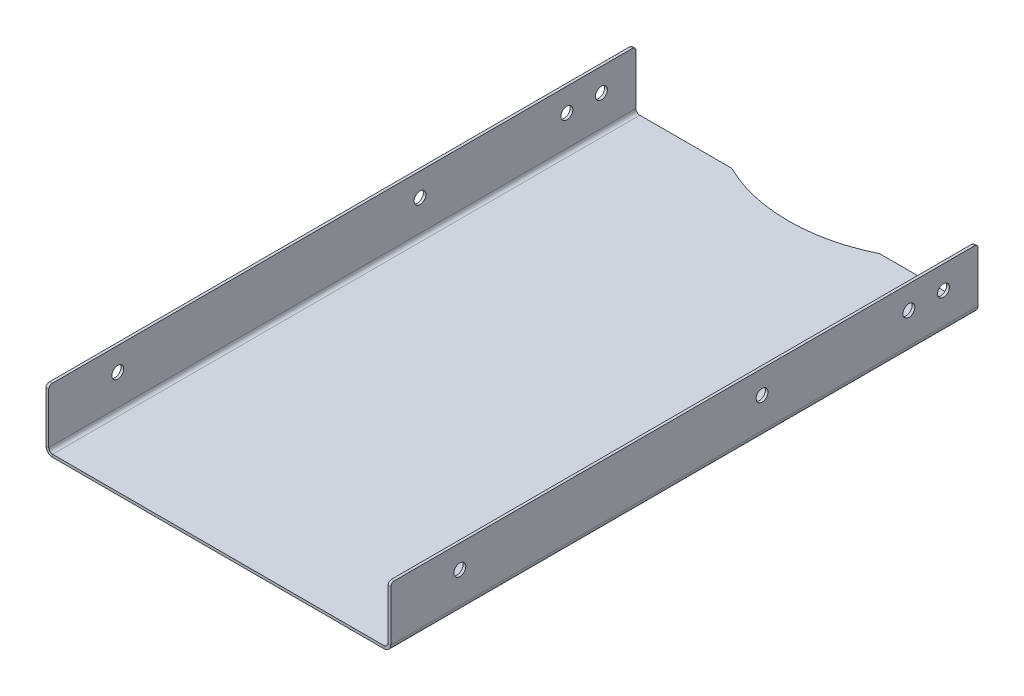
SolidWorks part; units mm, degrees
note: The reader was unsure of these and kept them because the rebuilt part matched: thickness of "Base-Flange1", "Edge-Flange1", "Sheet-Metal1", "Sheet-Metal2", "Sheet-Metal3", "Sheet-Metal4", "Sheet-Metal5", "Sheet-Metal6", "Sheet-Metal7"; flange length of "Edge-Flange1".
material "Plain Carbon Steel"
ref_plane "Front Plane" through (0, 0, 0) normal (0, 0, 1) x (1, 0, 0)
ref_plane "Top Plane" through (0, 0, 0) normal (0, 1, 0) x (1, 0, 0)
ref_plane "Right Plane" through (0, 0, 0) normal (1, 0, 0) x (0, 0, -1)
sketch "Sketch1" plane through (0, 0, 0) normal (0, 1, 0) x (1, 0, 0)
  line L1 (0, 0) -> (253.492, 0)
  line L2 (0, 0) -> (0, 457.2)
  line L3 (0, 457.2) -> (253.492, 457.2)
  line L4 (253.492, 0) -> (253.492, 457.2)
  dimension "D1" = 253.492
  dimension "D2" = 457.2
base flange "Base-Flange1" sketch "Sketch1" thickness 1.9939 reverse thickness direction no parameters "D1"=2.8461
edge flange "Edge-Flange1" sketch "Sketch10" flange profiles "Sketch10", "Sketch11" flange angle 90 flange length 44.45 flange position material inside bend radius 2.8461 thickness 1.9939 relief rectangular parameters "D1"=3, "D6"=10, "D8"=1
sketch "Sketch10" plane through (0, 0, 0) normal (-1, 0, 0) x (0, 0, 1)
  line L2 (-457.2, 0) -> (-457.2, 42.4561)
  line L3 (-457.2, 42.4561) -> (0, 42.4561)
  line L4 (0, 42.4561) -> (0, 0)
  line L7 (-457.2, 0) -> (0, 0) construction
  line L8 (-457.2, 0) -> (0, 0)
sketch "Sketch11" plane through (253.492, 0, 0) normal (1, 0, 0) x (0, 0, -1)
  line L2 (457.2, 0) -> (457.2, 42.4561)
  line L3 (457.2, 42.4561) -> (0, 42.4561)
  line L4 (0, 42.4561) -> (0, 0)
  line L5 (0, 0) -> (457.2, 0) construction
  line L6 (0, 0) -> (457.2, 0)
bend "EdgeBend1" bend radius 2.8461 bend angle 90 parameters "D5"=1
bend "EdgeBend2" bend radius 2.8461 bend angle 90 parameters "D5"=2
hole_wizard "Hole for 1/4 Self-clinching Nuts (S,SS,CLS,CLSS)1" positions "Sketch12" profile "Sketch13" hole size "1/4-20" standard "PEM® Inch" end condition through all
sketch "Sketch12" plane through (0, 0, 0) normal (-1, 0, 0) x (0, 0, 1)
  line L0 (-228.6, 42.4561) -> (-228.6, -1.9939) construction
  line L1 (0, 42.4561) -> (-457.2, 42.4561) construction
  line L2 (0, -1.9939) -> (-457.2, -1.9939) construction
  line L3 (-457.2, 42.4561) -> (-457.2, 2.8461) construction
  line L5 (0, 0) -> (-457.2, 0) construction
  line L6 (0, 0) -> (-457.2, 0) construction
  point P0 (-406.4, 25.4)
  point P26 (-50.8, 25.4)
  point P31 (-381, 25.4)
  point P36 (-273.05, 25.4)
  dimension "D1" = 25.4
  dimension "D2" = 50.8
  dimension "D4" = 107.95
  dimension "D5" = 25.4
sketch "Sketch13" plane through (0, 25.4, -406.4) normal (0, 1, 0) x (0, 0, 1)
  line L0 (0, 0) -> (0, 253.492)
  line L1 (0, 253.492) -> (4.3688, 253.492)
  line L2 (4.3688, 253.492) -> (4.3688, 0)
  line L5 (4.3688, 0) -> (0, 0)
  line L11 (0, -6.35) -> (0, 107.95) construction
  dimension "Thru Hole Dia." = 8.7376
  dimension "Thru Hole Depth" = 253.492
sketch "Sketch14" plane through (0, 0, 0) normal (0, 1, 0) x (1, 0, 0)
  line L0 (4.84, 0) -> (248.652, 0) construction
  line L6 (248.652, 457.2) -> (4.84, 457.2) construction
  line L7 (229.602, 457.2) -> (23.89, 457.2)
  line L8 (229.602, 457.2) -> (229.602, 487.68)
  line L9 (229.602, 487.68) -> (23.89, 487.68)
  line L10 (23.89, 457.2) -> (23.89, 487.68)
  line L11 (4.84, 0) -> (4.84, 457.2) construction
  point P6 (126.746, 0)
  point P9 (126.746, 457.2)
  dimension "D1" = 30.48
  dimension "D2" = 19.05
extrude "Boss-Extrude1" [suppressed] add sketch "Sketch14" against normal up to surface (2.3622 mm away)
sketch "Sketch15" plane through (0, -1.9939, 0) normal (0, -1, 0) x (1, 0, 0)
  line L0 (248.652, -457.2) -> (4.84, -457.2) construction
  line L1 (215.646, -457.2) -> (37.846, -457.2)
  arc A0 (37.846, -457.2) -> (215.646, -457.2) centre (126.746, -541.8667) cw
  point P3 (126.746, -457.2)
  point P9 (126.746, -419.1)
  dimension "D1" = 177.8
  dimension "D2" = 38.1
extrude "Cut-Extrude1" cut sketch "Sketch15" against normal through all normal cut yes
sketch "Sketch16" plane through (0, -1.9939, 0) normal (0, -1, 0) x (1, 0, 0)
  line L0 (253.492, 0) -> (253.492, -457.2) construction
  line L1 (0, -457.2) -> (253.492, -457.2)
  line L2 (0, -457.2) -> (0, -431.8)
  line L3 (0, -431.8) -> (253.492, -431.8)
  line L4 (253.492, -457.2) -> (253.492, -431.8)
  dimension "D1" = 25.4
extrude "Cut-Extrude2" cut sketch "Sketch16" against normal through all normal cut yes
sketch "Sketch17" [suppressed] plane through (0, 0, 0) normal (0, 1, 0) x (1, 0, 0)
  line L0 (121.9835, 0) -> (126.746, 8.2489)
  line L1 (4.7434, 0) -> (248.7485, 0) construction
  line L2 (126.746, 8.2489) -> (131.5085, 0)
  line L3 (131.5085, 0) -> (121.9835, 0)
  line L4 (253.492, 209.5962) -> (0, 209.5962) construction
  line L5 (253.492, 431.8) -> (253.492, 0) construction
  line L6 (0, 0) -> (0, 431.8) construction
  line L7 (131.5085, 419.1924) -> (121.9835, 419.1924)
  line L8 (126.746, 410.9435) -> (131.5085, 419.1924)
  line L9 (121.9835, 419.1924) -> (126.746, 410.9435)
  arc A0 (72.3678, 431.8) -> (181.1242, 431.8) centre (126.746, 541.8667) ccw construction
  point P4 (126.746, 0)
  point P6 (126.746, 419.1924)
  dimension "D1" = 9.525
extrude "Cut-Extrude3" [suppressed] cut sketch "Sketch17" against normal through all
fillet "Fillet1" radius 2.54 4 edges at (0.9969, 42.4561, -431.8) (252.4951, 42.4561, -431.8) (252.4951, 42.4561, 0) (0.9969, 42.4561, 0)
sketch "Bend-Lines1" [suppressed] plane through (0, 0, 0) normal (0, 1, 0) x (1, 0, 0)
sketch "Bounding-Box1" [suppressed] plane through (0, 0, 0) normal (0, 1, 0) x (1, 0, 0)
sheet metal parameters "Sheet-Metal1" thickness 1.9939 parameters "D1"=3, "D7"=2.3622
flat pattern "Flat-Pattern1" [suppressed]
sketch "Bend-Lines2" plane through (0, 0, 0) normal (0, 1, 0) x (1, 0, 0)
sketch3d "Bounding-Box2" [suppressed]
  line L0 (0, 0, 0) -> (0, 609.6, 0) construction
  line L1 (-247.65, 0, 0) -> (-247.65, 609.6, 0) construction
  line L2 (0, 0, 0) -> (-247.65, 0, 0) construction
  line L3 (0, 609.6, 0) -> (-247.65, 609.6, 0) construction
sheet metal parameters "Sheet-Metal2" thickness 1.9939 parameters "D1"=3, "D7"=2.3622
flat pattern "Flat-Pattern1"
sketch "Bend-Lines2" plane through (0, 0, 0) normal (0, 1, 0) x (1, 0, 0)
  line L0 (247.9338, 0) -> (247.9338, 609.6) construction
  line L1 (-0.2838, 609.6) -> (-0.2838, 0) construction
  line L2 (247.9338, 0) -> (247.9338, 609.6) construction
  line L3 (-0.2838, 609.6) -> (-0.2838, 0) construction
sketch3d "Bounding-Box2" [suppressed]
  line L0 (-42.6555, 0, 0) -> (-42.6555, 609.6, 0) construction
  line L1 (290.3055, 0, 0) -> (290.3055, 609.6, 0) construction
  line L2 (-42.6555, 0, 0) -> (290.3055, 0, 0) construction
  line L3 (-42.6555, 609.6, 0) -> (290.3055, 609.6, 0) construction
bend of the flat pattern "Flatten-<EdgeBend1>1"
bend of the flat pattern "Flatten-<EdgeBend2>1"
sheet metal parameters "Sheet-Metal3" thickness 1.9939 parameters "D1"=3, "D7"=2.3622
flat pattern "Flat-Pattern1"
sketch "Bend-Lines2" plane through (0, 0, 0) normal (0, 1, 0) x (1, 0, 0)
  line L0 (252.2369, 0) -> (252.2369, 457.2) construction
  line L1 (1.7631, 457.2) -> (1.7631, 0) construction
  line L2 (252.2369, 0) -> (252.2369, 457.2) construction
  line L3 (1.7631, 457.2) -> (1.7631, 0) construction
sketch3d "Bounding-Box2" [suppressed]
  line L0 (-40.9239, 0, 0) -> (-40.9239, 457.2, 0) construction
  line L1 (294.9239, 0, 0) -> (294.9239, 457.2, 0) construction
  line L2 (-40.9239, 0, 0) -> (294.9239, 0, 0) construction
  line L3 (-40.9239, 457.2, 0) -> (294.9239, 457.2, 0) construction
bend of the flat pattern "Flatten-<EdgeBend1>1"
bend of the flat pattern "Flatten-<EdgeBend2>1"
sheet metal parameters "Sheet-Metal4" thickness 1.9939 parameters "D1"=3, "D7"=2.3622
flat pattern "Flat-Pattern1"
sketch "Bend-Lines2" plane through (0, 0, 0) normal (0, 1, 0) x (1, 0, 0)
  line L0 (247.9338, 0) -> (247.9338, 609.6) construction
  line L1 (-0.2838, 609.6) -> (-0.2838, 0) construction
  line L2 (247.9338, 0) -> (247.9338, 609.6) construction
  line L3 (-0.2838, 609.6) -> (-0.2838, 0) construction
sketch3d "Bounding-Box2" [suppressed]
  line L0 (-42.6555, 0, 0) -> (-42.6555, 640.08, 0) construction
  line L1 (290.3055, 0, 0) -> (290.3055, 640.08, 0) construction
  line L2 (-42.6555, 0, 0) -> (290.3055, 0, 0) construction
  line L3 (-42.6555, 640.08, 0) -> (290.3055, 640.08, 0) construction
bend of the flat pattern "Flatten-<EdgeBend1>1"
bend of the flat pattern "Flatten-<EdgeBend2>1"
sheet metal parameters "Sheet-Metal5" thickness 1.9939 parameters "D1"=3, "D7"=2.3622
flat pattern "Flat-Pattern1"
sketch "Bend-Lines2" plane through (0, 0, 0) normal (0, 1, 0) x (1, 0, 0)
  line L0 (251.7289, 0) -> (251.7289, 457.2) construction
  line L1 (1.7631, 457.2) -> (1.7631, 0) construction
  line L2 (251.7289, 0) -> (251.7289, 457.2) construction
  line L3 (1.7631, 457.2) -> (1.7631, 0) construction
sketch3d "Bounding-Box2" [suppressed]
  line L0 (-40.9239, 0, 0) -> (-40.9239, 457.2, 0) construction
  line L1 (294.4159, 0, 0) -> (294.4159, 457.2, 0) construction
  line L2 (-40.9239, 0, 0) -> (294.4159, 0, 0) construction
  line L3 (-40.9239, 457.2, 0) -> (294.4159, 457.2, 0) construction
bend of the flat pattern "Flatten-<EdgeBend1>1"
bend of the flat pattern "Flatten-<EdgeBend2>1"
sheet metal parameters "Sheet-Metal6" [suppressed] thickness 1.9939 parameters "D1"=3, "D7"=2.3622
flat pattern "Flat-Pattern1"
sketch "Bend-Lines2" plane through (0, 0, 0) normal (0, 1, 0) x (1, 0, 0)
  line L0 (251.6703, 0) -> (251.6703, 431.8) construction
  line L1 (1.8217, 431.8) -> (1.8217, 0) construction
  line L2 (251.6703, 0) -> (251.6703, 431.8) construction
  line L3 (1.8217, 431.8) -> (1.8217, 0) construction
sketch3d "Bounding-Box2" [suppressed]
  line L0 (-40.8067, 0, 0) -> (-40.8067, 431.8, 0) construction
  line L1 (294.2987, 0, 0) -> (294.2987, 431.8, 0) construction
  line L2 (-40.8067, 0, 0) -> (294.2987, 0, 0) construction
  line L3 (-40.8067, 431.8, 0) -> (294.2987, 431.8, 0) construction
bend of the flat pattern "Flatten-<EdgeBend1>1"
bend of the flat pattern "Flatten-<EdgeBend2>1"
sheet metal parameters "Sheet-Metal7" thickness 1.9939 parameters "D1"=3, "D7"=2.3622
flat pattern "Flat-Pattern1"
sketch "Bend-Lines2" plane through (0, 0, 0) normal (0, 1, 0) x (1, 0, 0)
  line L0 (251.6703, 0) -> (251.6703, 431.8) construction
  line L1 (1.8217, 431.8) -> (1.8217, 0) construction
  line L2 (251.6703, 0) -> (251.6703, 431.8) construction
  line L3 (1.8217, 431.8) -> (1.8217, 0) construction
sketch3d "Bounding-Box2" [suppressed]
  line L0 (-40.8067, 0, 0) -> (-40.8067, 431.8, 0) construction
  line L1 (294.2987, 0, 0) -> (294.2987, 431.8, 0) construction
  line L2 (-40.8067, 0, 0) -> (294.2987, 0, 0) construction
  line L3 (-40.8067, 431.8, 0) -> (294.2987, 431.8, 0) construction
bend of the flat pattern "Flatten-<EdgeBend1>1"
bend of the flat pattern "Flatten-<EdgeBend2>1"
